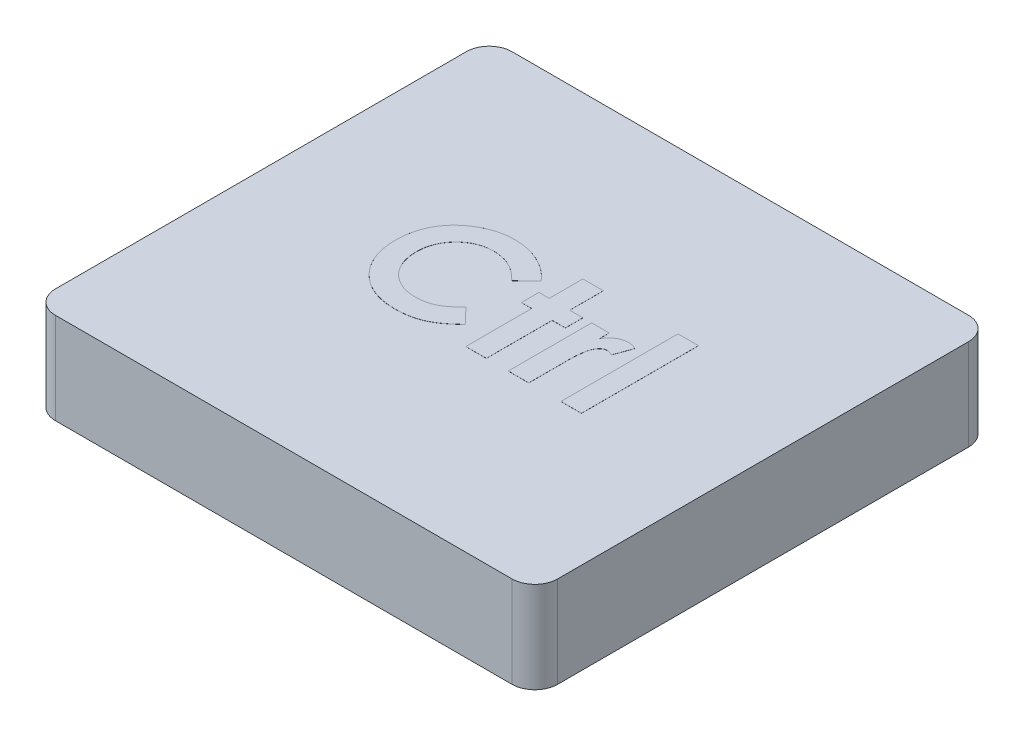
SolidWorks part; units mm, degrees
ref_plane "Front Plane" through (0, 0, 0) normal (0, 0, 1) x (1, 0, 0)
ref_plane "Top Plane" through (0, 0, 0) normal (0, 1, 0) x (1, 0, 0)
ref_plane "Right Plane" through (0, 0, 0) normal (1, 0, 0) x (0, 0, -1)
sketch "Sketch1" plane through (0, 0, 0) normal (0, 1, 0) x (1, 0, 0)
  line L0 (0, 0) -> (13.97, 0)
  line L1 (13.97, 0) -> (13.97, 12.7)
  line L2 (13.97, 12.7) -> (0, 12.7)
  line L3 (0, 12.7) -> (0, 0)
  dimension "D1" = 13.97
  dimension "D2" = 12.7
extrude "Boss-Extrude1" add sketch "Sketch1" along normal blind 2.54
fillet "Fillet1" radius 0.635 4 edges at (0, 1.27, -12.7) (13.97, 1.27, -12.7) (13.97, 1.27, 0) (0, 1.27, 0)
shell "Shell1" thickness 0.635 removed face at (6.985, 0, -6.35)
sketch "Sketch2" plane through (0, 1.905, 0) normal (0, -1, 0) x (-1, 0, 0)
  line L0 (-0.635, 6.35) -> (-13.335, 6.35) construction
  line L1 (-0.635, 12.065) -> (-0.635, 0.635) construction
  line L2 (-13.335, 0.635) -> (-13.335, 12.065) construction
  line L3 (-6.985, 0.635) -> (-6.985, 12.065) construction
  line L4 (-0.635, 0.635) -> (-13.335, 0.635) construction
  line L5 (-13.335, 12.065) -> (-0.635, 12.065) construction
  circle A0 centre (-6.985, 6.35) radius 2.54
  dimension "D1" = 5.08
extrude "Boss-Extrude2" add sketch "Sketch2" along normal up to surface (1.905 mm away) up to face at (6.985, 0, -6.35)
sketch "Sketch3" plane through (0, 2.54, 0) normal (0, 1, 0) x (1, 0, 0)
  line L0 (0, 12.065) -> (0, 0.635) construction
  line L1 (13.335, 12.7) -> (0.635, 12.7) construction
  text T0 "<b>Ctrl</b>"
  dimension "D1" = 3.3528
  dimension "D2" = 7.747
extrude "Boss-Extrude3" add sketch "Sketch3" along normal blind 0.0025
equation "\".3`\"=0.304046"
